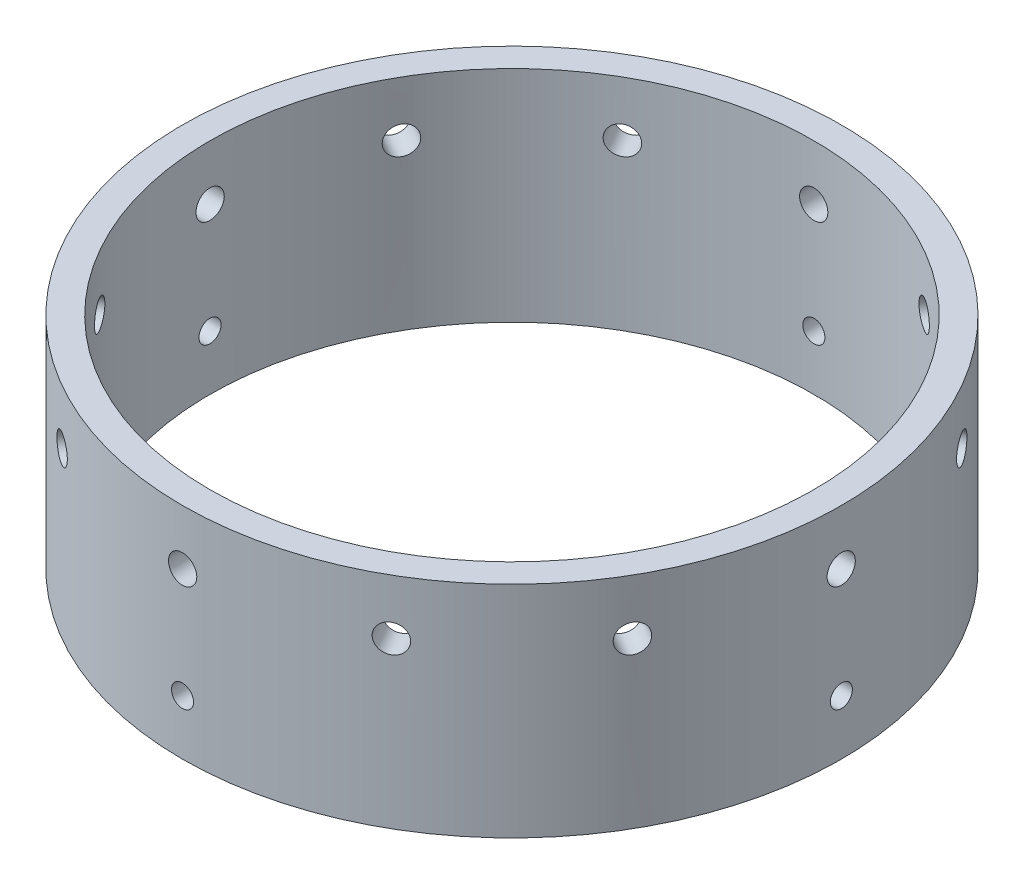
SolidWorks part; units mm, degrees
ref_plane "Front Plane" through (0, 0, 0) normal (0, 0, 1) x (1, 0, 0)
ref_plane "Top Plane" through (0, 0, 0) normal (0, 1, 0) x (1, 0, 0)
ref_plane "Right Plane" through (0, 0, 0) normal (1, 0, 0) x (0, 0, -1)
sketch "Sketch2" plane through (0, 0, 0) normal (0, 1, 0) x (1, 0, 0)
  circle A0 centre (0, 0) radius 76.2
  circle A1 centre (0, 0) radius 69.85
  dimension "D1" = 139.7
  dimension "D2" = 152.4
extrude "Boss-Extrude1" add sketch "Sketch2" along normal blind 50.8
sketch "Sketch3" plane through (0, 0, 0) normal (0, 0, 1) x (1, 0, 0)
  line L0 (-76.2, 0) -> (76.2, 0) construction
  line L1 (76.2, 50.8) -> (-76.2, 50.8) construction
  line L2 (76.2, 50.8) -> (-76.2, 50.8) construction
  line L3 (-76.2, 0) -> (76.2, 0) construction
  line L4 (0, 25.4) -> (0, 50.8) construction
  line L7 (-76.2, 25.4) -> (76.2, 25.4) construction
  line L8 (-76.2, 50.8) -> (-76.2, 0) construction
  line L9 (76.2, 0) -> (76.2, 50.8) construction
  line L11 (0, 0) -> (0, 25.4) construction
  circle A0 centre (0, 12.7) radius 3.2639
  circle A1 centre (0, 38.1) radius 3.2639
  point P16 (0, 0)
  point P17 (0, 12.7)
  point P18 (0, 42.8074)
  dimension "D2" = 6.5278
  dimension "D1" = 6.5278
  dimension "D3" = 12.7
  dimension "D4" = 12.7
extrude "Cut-Extrude1" cut sketch "Sketch3" against normal through all contours A1
pattern_circular "CirPattern1" count 12 over 360 about axis through (0, 50.8, 0) along (0, 1, 0) of "Cut-Extrude1"
ref_plane "Plane1" through (0, 0, 76.2) normal (0, 0, 1) x (1, 0, 0)
sketch "Sketch7" plane through (0, 0, 76.2) normal (0, 0, 1) x (1, 0, 0)
  circle A1 centre (0, 38.1) radius 3.2639
  circle A2 centre (0, 38.1) radius 3.2639 construction
  circle A3 centre (0, 12.7) radius 3.2639
  circle A4 centre (0, 12.7) radius 3.2639 construction
  point P0 (0, 12.7)
  point P1 (0, 12.7)
  dimension "D1" = 0
  dimension "D2" = 0
hole_wizard "1/4-20 Tapped Hole2" positions "Sketch7" profile "Sketch8" tap size "1/4-20" standard "ANSI Inch" end condition up to next
sketch "Sketch8" plane through (0, 12.7, 76.2) normal (1, 0, 0) x (0, -1, 0)
  line L0 (0, 0) -> (0, 6.35)
  line L1 (0, 6.35) -> (2.5527, 6.35)
  line L2 (2.5527, 6.35) -> (2.5527, 0)
  line L5 (2.5527, 0) -> (0, 0)
  line L11 (0, -6.35) -> (0, 107.95) construction
  dimension "Thru Tap Drill Dia." = 5.1054
  dimension "Thru Tap Drill Depth" = 6.35
cosmetic thread "Hole Thread2" parameters "D2"=6.35
pattern_circular "CirPattern3" count 4 over 360 about axis through (0, 50.8, 0) along (0, 1, 0) of "1/4-20 Tapped Hole2"
cosmetic thread "Hole Thread3" parameters "D2"=6.35
cosmetic thread "Hole Thread4" parameters "D2"=6.35
cosmetic thread "Hole Thread5" parameters "D2"=6.35
